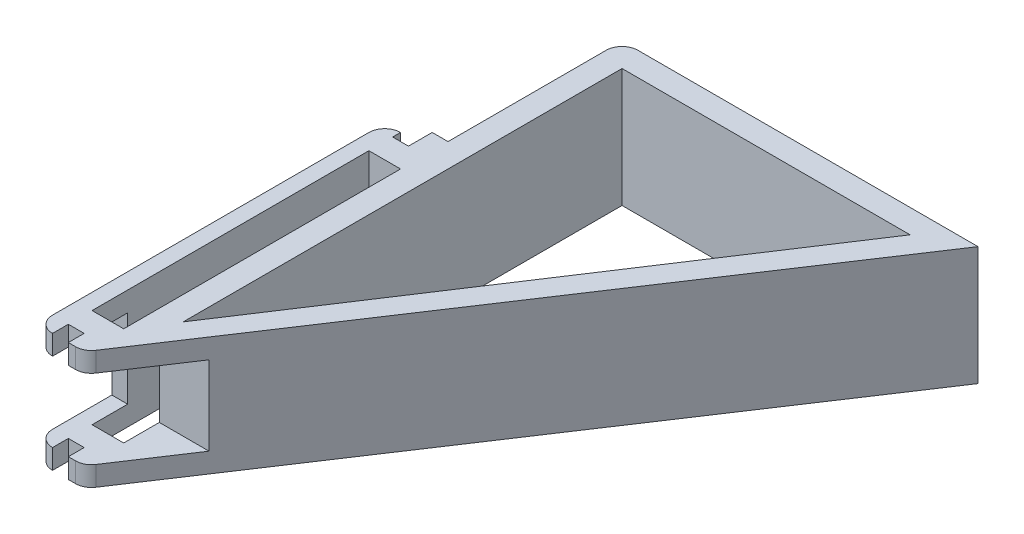
SolidWorks part; units mm, degrees
ref_plane "Front Plane" through (0, 0, 0) normal (0, 0, 1) x (1, 0, 0)
ref_plane "Top Plane" through (0, 0, 0) normal (0, 1, 0) x (1, 0, 0)
ref_plane "Right Plane" through (0, 0, 0) normal (1, 0, 0) x (0, 0, -1)
sketch "Sketch2" plane through (0, 0, 0) normal (0, 1, 0) x (1, 0, 0)
  line L0 (0, 0) -> (0, 2)
  line L1 (0, 2) -> (2, 2)
  line L2 (2, 2) -> (2, 0)
  line L3 (2, 0) -> (4, 0)
  line L4 (4, 0) -> (4, 46)
  line L5 (4, 46) -> (2, 46)
  line L6 (2, 46) -> (2, 43)
  line L7 (2, 43) -> (0, 43)
  line L8 (0, 43) -> (0, 44)
  line L9 (0, 44) -> (-2, 44)
  line L10 (-2, 44) -> (-2, 0)
  line L11 (-2, 0) -> (0, 0)
  line L12 (4, 0) -> (49, 68)
  line L13 (49, 68) -> (4, 68)
  line L14 (4, 68) -> (4, 46)
  line L15 (43.4173, 65) -> (45.9191, 63.3444)
  line L17 (0, 40) -> (4, 40)
  line L18 (7, 65) -> (43.4173, 65)
  line L19 (7, 9.5162) -> (43.4173, 65)
  line L20 (7, 65) -> (7, 9.5162)
  line L21 (0, 40) -> (0, 5)
  line L22 (0, 5) -> (4, 5)
  line L23 (4, 40) -> (4, 5)
  dimension "D1" = 41
  dimension "D2" = 2
  dimension "D3" = 2
  dimension "D4" = 6
  dimension "D5" = 2
  dimension "D6" = 1
  dimension "D7" = 2
  dimension "D8" = 3
  dimension "D9" = 22
  dimension "D10" = 45
  dimension "D11" = 3
  dimension "D12" = 3
  dimension "D13" = 3
  dimension "D14" = 3
  dimension "D15" = 3
extrude "Boss-Extrude1" add sketch "Sketch2" along normal blind 15 contours L10 L11 L0 L1 L2 L3 L4 L5 L6 L7 L8 L9 | L13 L14 L4 L12 region at (-0.082, 0, -22.5164) region at (4.8154, 0, -2.5)
sketch "Sketch3" plane through (-2, 0, 0) normal (-1, 0, 0) x (0, 0, 1)
  line L0 (0, 0) -> (0, 2.5)
  line L1 (0, 15) -> (0, 0) construction
  line L2 (0, 15) -> (0, 12.5)
  line L3 (0, 2.5) -> (-9.5, 2.5)
  line L4 (-9.5, 2.5) -> (-9.5, 12.5)
  line L5 (-9.5, 12.5) -> (0, 12.5)
  dimension "D1" = 2.5
  dimension "D2" = 2.5
  dimension "D3" = 9.5
extrude "Cut-Extrude1" cut sketch "Sketch3" against normal blind 15 and the other way through all
fillet "Fillet1" radius 2 1 edges at (-2, 7.5, -44) type face fillet first side face at (-2, 7.5, -13.375) second side face at (-1, 7.5, -44)
fillet "Fillet2" radius 2 1 edges at (4, 7.5, -68) type face fillet first side face at (4, 7.5, -57) second side face at (26.5, 7.5, -68)
fillet "Fillet3" radius 2 1 edges at (4, 1.25, 0) type face fillet first side face at (16.8217, 7.5, -19.375) first side face at (3, 13.75, 0) second side face at (3, 1.25, 0)
fillet "Fillet4" radius 2 1 edges at (4, 13.75, 0) type face fillet first side face at (16.97, 7.5, -19.5991) second side face at (3, 13.75, 0)
fillet "Fillet5" radius 2 1 edges at (-2, 13.75, 0) type face fillet first side face at (-1, 13.75, 0) second side face at (-2, 7.5, -12.875)
fillet "Fillet6" radius 2 1 edges at (-2, 1.25, 0) type face fillet first side face at (-1, 1.25, 0) second side face at (-2, 7.5, -13.375)
